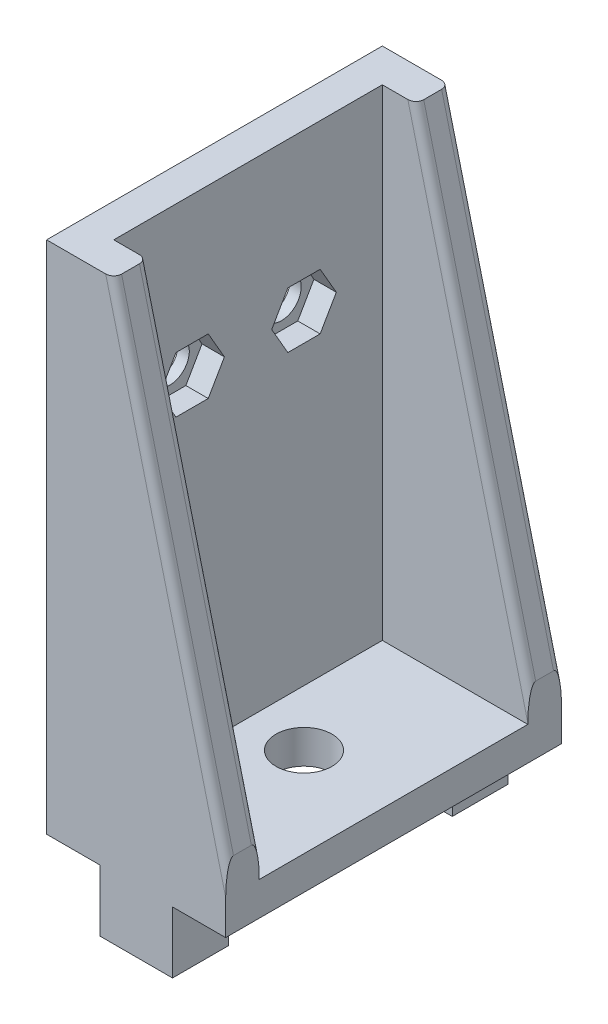
SolidWorks part; units mm, degrees
ref_plane "Front Plane" through (0, 0, 0) normal (0, 0, 1) x (1, 0, 0)
ref_plane "Top Plane" through (0, 0, 0) normal (0, 1, 0) x (1, 0, 0)
ref_plane "Right Plane" through (0, 0, 0) normal (1, 0, 0) x (0, 0, -1)
sketch "Sketch1" plane through (0, 0, 0) normal (0, 1, 0) x (1, 0, 0)
  line L1 (-8, 0) -> (8, 0)
  line L2 (-8, 0) -> (-8, 30)
  line L3 (-8, 30) -> (8, 30)
  line L4 (8, 0) -> (8, 30)
  line L5 (-3.25, 30) -> (3.25, 30)
  line L6 (-3.25, 30) -> (-3.25, 25)
  line L7 (-3.25, 25) -> (3.25, 25)
  line L8 (3.25, 30) -> (3.25, 25)
  line L9 (-3.25, 0) -> (3.25, 0)
  line L10 (-3.25, 0) -> (-3.25, 5)
  line L11 (-3.25, 5) -> (3.25, 5)
  line L12 (3.25, 0) -> (3.25, 5)
  circle A0 centre (0, 15) radius 2.5
  point P4 (0, 0)
  point P10 (0, 30)
  point P11 (-8, 15)
  point P18 (0, 5)
  point P19 (0, 25)
  dimension "D3" = 5
  dimension "D1" = 16
  dimension "D2" = 30
  dimension "D4" = 6.5
  dimension "D5" = 5
extrude "Boss-Extrude1" add sketch "Sketch1" along normal blind 3 contours L12 L1 L4 L3 L8 L7 L6 L2 L10 L11 A0 | L1 L12 L11 L10 | L8 L3 L6 L7 region at (-7.66, 0, -15) region at (0, 0, -2.5) region at (0, 0, -27.5)
extrude "Boss-Extrude2" add sketch "Sketch1<3>" against normal blind 5.5 contours L8 L3 L6 L7 | L1 L12 L11 L10 region at (0, 0, -2.5) region at (0, 0, -27.5)
sketch "Sketch1<3>" plane through (0, 0, 0) normal (0, 1, 0) x (1, 0, 0) same geometry as "Sketch1"
sketch "Sketch2" plane through (0, 3, 0) normal (0, 1, 0) x (1, 0, 0)
  line L0 (-8, 30) -> (8, 30) construction
  line L1 (-8, 0) -> (-5, 0)
  line L2 (-8, 0) -> (-8, 30)
  line L3 (-8, 30) -> (-5, 30)
  line L4 (-5, 0) -> (-5, 30)
  line L5 (8, 0) -> (8, 30) construction
  line L6 (-8, 0) -> (8, 0)
  line L7 (-8, 0) -> (-8, 3)
  line L8 (-8, 3) -> (8, 3)
  line L9 (8, 0) -> (8, 3)
  line L11 (-8, 30) -> (8, 30)
  line L12 (-8, 30) -> (-8, 27)
  line L13 (-8, 27) -> (8, 27)
  line L14 (8, 30) -> (8, 27)
  circle A0 centre (0, 15) radius 4.5
  line M6 (8, 30) -> (-8, 30)
  line M7 (-8, 30) -> (-8, 0)
  line M8 (-8, 0) -> (8, 0)
  line M9 (8, 0) -> (8, 30)
  dimension "D1" = 9
  dimension "D2" = 3
extrude "Boss-Extrude3" add sketch "Sketch2" along normal blind 46 from surface contours L13 L2 L8 L4 | L8 L2 L4 M8 | L13 L4 M7 M6 | L4 L13 M9 M6 | L8 L4 M8 M9 region at (-6.5, 3, -1.5) region at (1.5, 3, -1.5) region at (-6.5, 3, -15) region at (-6.5, 3, -28.5) region at (1.5, 3, -28.5) starting at face at (0, 0, -12.5)
sketch "Sketch3" plane through (0, 0, -30) normal (0, 0, -1) x (-1, 0, 0)
  line L0 (2, 46) -> (-8, 6)
  line L1 (-8, 46) -> (8, 46) construction
  line L2 (-8, 46) -> (-8, 0) construction
  line M8 (8, 46) -> (-8, 46)
  line M9 (-8, 46) -> (-8, 0)
  dimension "D1" = 3
  dimension "D2" = 3
extrude "Cut-Extrude1" cut sketch "Sketch3" against normal through all and the other way through all contours L0 M8 M9 region at (4.6667, 32.6667, -30)
sketch "Sketch4" plane through (-8, 0, 0) normal (-1, 0, 0) x (0, 0, 1)
  line L0 (-10, 32) -> (-20, 32) construction
  line L1 (-30, 46) -> (0, 46) construction
  line L2 (-8.5566, 29.5) -> (-7.1132, 32)
  line L3 (-7.1132, 32) -> (-8.5566, 34.5)
  line L4 (-8.5566, 34.5) -> (-11.4434, 34.5)
  line L5 (-11.4434, 34.5) -> (-12.8868, 32)
  line L6 (-12.8868, 32) -> (-11.4434, 29.5)
  line L7 (-11.4434, 29.5) -> (-8.5566, 29.5)
  line L8 (-18.5566, 29.5) -> (-17.1132, 32)
  line L9 (-17.1132, 32) -> (-18.5566, 34.5)
  line L10 (-18.5566, 34.5) -> (-21.4434, 34.5)
  line L11 (-21.4434, 34.5) -> (-22.8868, 32)
  line L12 (-22.8868, 32) -> (-21.4434, 29.5)
  line L13 (-21.4434, 29.5) -> (-18.5566, 29.5)
  circle A0 centre (-10, 32) radius 1.75
  circle A1 centre (-20, 32) radius 1.75
  circle A2 centre (-10, 32) radius 2.5 construction
  circle A3 centre (-20, 32) radius 2.5 construction
  point P20 (-15, 46)
  point P21 (-15, 32)
  dimension "D4" = 3.5
  dimension "D1" = 5
  dimension "D2" = 14
  dimension "D3" = 10
extrude "Cut-Extrude2" cut sketch "Sketch4" against normal through all from offset 1 offset against normal yes
extrude "Cut-Extrude3" cut sketch "Sketch4<2>" against normal through all contours A1 | A0 region at (-8, 32, -10) region at (-8, 32, -20)
sketch "Sketch4<2>" plane through (-8, 0, 0) normal (-1, 0, 0) x (0, 0, 1) same geometry as "Sketch4"
fillet "Fillet1" radius 0.7 4 edges at (3, 26, -27) (3, 26, 0) (3, 26, -3)
